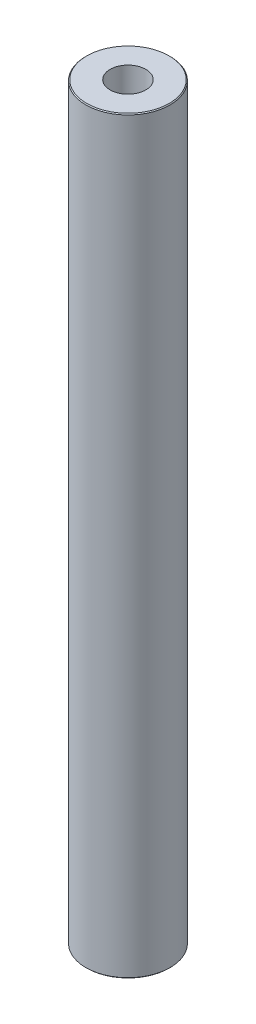
SolidWorks part; units mm, degrees
ref_plane "Front Plane" through (0, 0, 0) normal (0, 0, 1) x (1, 0, 0)
ref_plane "Top Plane" through (0, 0, 0) normal (0, 1, 0) x (1, 0, 0)
ref_plane "Right Plane" through (0, 0, 0) normal (1, 0, 0) x (0, 0, -1)
sketch "Sketch1" plane through (0, 0, 0) normal (0, 1, 0) x (1, 0, 0)
  circle A0 centre (0, 0) radius 20
  dimension "SHAFT_OD" = 40
extrude "Boss-Extrude1" add sketch "Sketch1" along normal blind 355.8843
sketch "Sketch2" plane through (0, 0, 0) normal (0, 1, 0) x (1, 0, 0)
  circle A0 centre (0, 0) radius 8.49
  dimension "BORE_D" = 16.98
extrude "Cut-Extrude1" cut sketch "Sketch2" along normal through all
chamfer "Chamfer1" distance 0.4199 angle 45 2 edges at (0, 355.8843, 20) (0, 0, 20)
